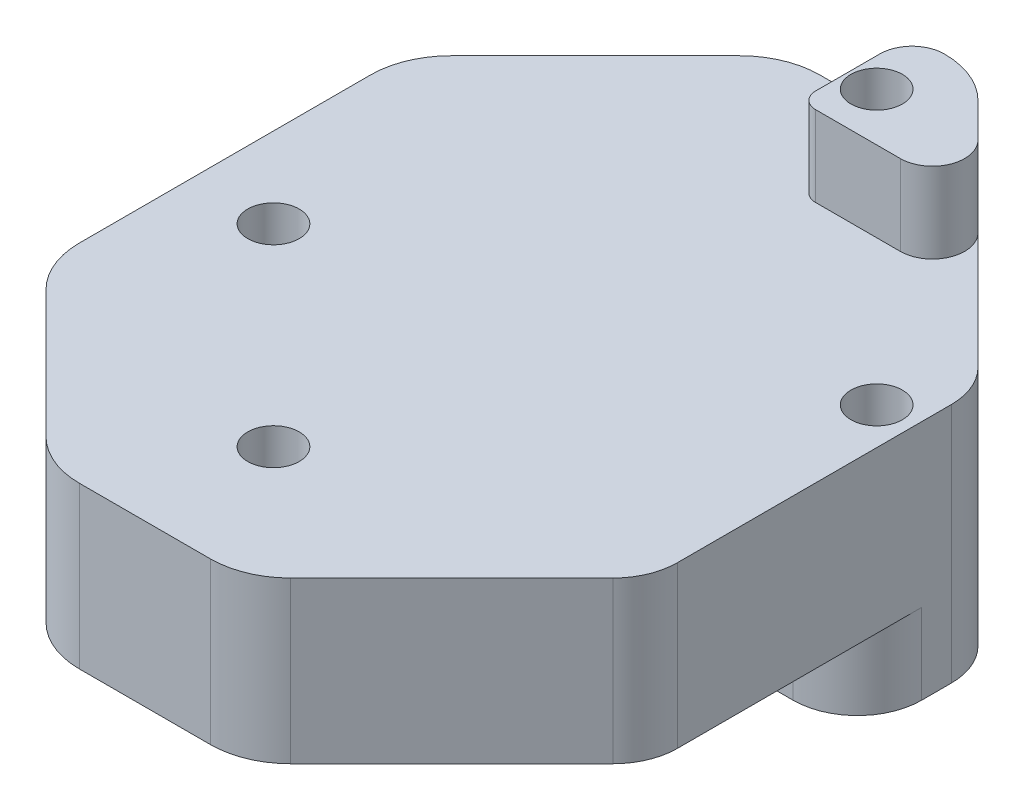
SolidWorks part; units mm, degrees
material "尼龙 101"
ref_plane "前视基准面" through (0, 0, 0) normal (0, 0, 1) x (1, 0, 0)
ref_plane "上视基准面" through (0, 0, 0) normal (0, 1, 0) x (1, 0, 0)
ref_plane "右视基准面" through (0, 0, 0) normal (1, 0, 0) x (0, 0, -1)
sketch "草图1" plane through (0, 0, 0) normal (0, 1, 0) x (1, 0, 0)
  line L0 (6.8, 37) -> (21.8, 22)
  line L1 (21.8, 22) -> (21.8, -8)
  line L2 (21.8, -8) -> (-17, -8)
  line L3 (-17, -8) -> (-17, 37)
  line L4 (-17, 37) -> (6.8, 37)
  circle A0 centre (0, 0) radius 1.6
  circle A1 centre (-12, 12) radius 1.6
  circle A2 centre (4.5, 33) radius 1.6
  circle A3 centre (16.5, 21) radius 1.6
  dimension "D1" = 12
  dimension "D2" = 3.2
  dimension "D3" = 12
  dimension "D4" = 16.5
  dimension "D5" = 21
  dimension "D6" = 12
  dimension "D7" = 12
  dimension "D10" = 5.3
  dimension "D9" = 5
  dimension "D8" = 135
  dimension "D11" = 8
  dimension "D12" = 30
  dimension "D13" = 45
extrude "凸台-拉伸1" add sketch "草图1" along normal blind 10
sketch "草图2" plane through (0, 0, 0) normal (0, -1, 0) x (1, 0, 0)
  line L0 (21.8, -17.5) -> (2, -17.5)
  line L1 (21.8, 8) -> (21.8, -22) construction
  line L2 (0, -19.5) -> (0, -37)
  line L3 (6.8, -37) -> (-17, -37) construction
  line L4 (0, -37) -> (6.8, -37)
  line L5 (6.8, -37) -> (21.8, -22)
  line L6 (21.8, -22) -> (21.8, -17.5)
  circle A0 centre (4.5, -33) radius 1.6 construction
  arc A2 (2, -17.5) -> (0, -19.5) centre (2, -19.5) ccw
  circle A3 centre (4.5, -33) radius 1.6
  circle A4 centre (16.5, -21) radius 1.6
  dimension "D1" = 15.5
  dimension "D2" = 2
  dimension "D3" = 3.2
  dimension "D4" = 3.2
extrude "凸台-拉伸2" add sketch "草图2" along normal blind 5
sketch "草图3" plane through (0, 10, 0) normal (0, 1, 0) x (1, 0, 0)
  line L0 (-5.1, 37) -> (-17, 25.1)
  line L1 (6.8, 37) -> (-17, 37) construction
  line L2 (-17, 37) -> (-17, -8) construction
  line L3 (-17, 25.1) -> (-17, 2.8579)
  line L4 (-17, 2.8579) -> (-6.1421, -8)
  line L5 (-17, -8) -> (21.8, -8) construction
  line L6 (-6.1421, -8) -> (6.1421, -8)
  line L7 (6.1421, -8) -> (21.8, 7.6579)
  line L8 (21.8, -8) -> (21.8, 22) construction
  line L9 (21.8, 7.6579) -> (21.8, 22)
  line L10 (21.8, 22) -> (6.8, 37) construction
  line L11 (21.8, 22) -> (6.8, 37)
  line L12 (6.8, 37) -> (-5.1, 37)
  circle A0 centre (0, 0) radius 1.6 construction
  dimension "D3" = 10
  dimension "D1" = 135
  dimension "D2" = 135
  dimension "D4" = 10
extrude "切除-拉伸1" cut sketch "草图3" against normal through all flip side to cut
fillet "圆角1" radius 5 8 edges at (21.8, 5, -7.6579) (6.1421, 5, 8) (-6.1421, 5, 8) (-17, 5, -2.8579) (-17, 5, -25.1) (-5.1, 5, -37) (21.8, 2.5, -22) (6.8, 2.5, -37)
fillet "圆角2" radius 2 2 edges at (0, -2.5, -37) (21.8, -2.5, -17.5)
sketch "草图4" plane through (0, 10, 0) normal (0, 1, 0) x (1, 0, 0)
  line L0 (2.7, 37) -> (2.7, 31)
  line L1 (4.7289, 37) -> (-3.0289, 37) construction
  line L2 (3.7, 30) -> (13.8, 30)
  line L3 (20.3355, 23.4645) -> (8.2645, 35.5355) construction
  line L4 (13.8, 30) -> (8.2645, 35.5355)
  line L5 (4.7289, 37) -> (2.7, 37)
  arc A0 (8.2645, 35.5355) -> (4.7289, 37) centre (4.7289, 32) ccw
  circle A1 centre (4.5, 33) radius 1.6 construction
  arc A2 (2.7, 31) -> (3.7, 30) centre (3.7, 31) ccw
  circle A3 centre (4.5, 33) radius 1.6
  dimension "D1" = 1.8
  dimension "D3" = 1
  dimension "D4" = 3.2
  dimension "D2" = 3
extrude "凸台-拉伸3" add sketch "草图4" along normal blind 5
fillet "圆角3" radius 2 2 edges at (2.7, 12.5, -37) (13.8, 12.5, -30)
sketch "草图5" plane through (0, 10, 0) normal (0, 1, 0) x (1, 0, 0)
  line L0 (18.8, 25) -> (18.8, 4.6579)
  line L1 (20.3355, 23.4645) -> (10.3858, 33.4142) construction
  line L2 (7.6066, -6.5355) -> (20.3355, 6.1934) construction
  line L13 (8.9716, 30) -> (3.7, 30)
  line L14 (2.7, 31) -> (2.7, 35)
  line L15 (4.7, 37) -> (-3.0289, 37)
  line L16 (-6.5645, 35.5355) -> (-15.5355, 26.5645)
  line L17 (-17, 23.0289) -> (-17, 4.9289)
  line L18 (-15.5355, 1.3934) -> (-7.6066, -6.5355)
  line L19 (-4.0711, -8) -> (4.0711, -8)
  line L20 (7.6066, -6.5355) -> (20.3355, 6.1934)
  line L21 (21.8, 9.7289) -> (21.8, 19.9289)
  line L22 (20.3355, 23.4645) -> (10.3858, 33.4142)
  line L30 (18.8, 4.6579) -> (20.3355, 6.1934)
  line L31 (21.8, 9.7289) -> (21.8, 19.9289)
  line L32 (20.3355, 23.4645) -> (18.8, 25)
  arc A8 (2.7, 31) -> (3.7, 30) centre (3.7, 31) ccw
  arc A9 (4.7, 37) -> (2.7, 35) centre (4.7, 35) ccw
  arc A12 (-3.0289, 37) -> (-6.5645, 35.5355) centre (-3.0289, 32) ccw
  arc A13 (-15.5355, 26.5645) -> (-17, 23.0289) centre (-12, 23.0289) ccw
  arc A14 (-17, 4.9289) -> (-15.5355, 1.3934) centre (-12, 4.9289) ccw
  arc A15 (-7.6066, -6.5355) -> (-4.0711, -8) centre (-4.0711, -3) ccw
  arc A16 (4.0711, -8) -> (7.6066, -6.5355) centre (4.0711, -3) ccw
  arc A17 (20.3355, 6.1934) -> (21.8, 9.7289) centre (16.8, 9.7289) ccw
  arc A18 (21.8, 19.9289) -> (20.3355, 23.4645) centre (16.8, 19.9289) ccw
  arc A19 (8.9716, 30) -> (10.3858, 33.4142) centre (8.9716, 32) ccw
  arc A27 (20.3355, 6.1934) -> (21.8, 9.7289) centre (16.8, 9.7289) ccw
  arc A28 (21.8, 19.9289) -> (20.3355, 23.4645) centre (16.8, 19.9289) ccw
  dimension "D2" = 3
  dimension "D1" = 0
extrude "切除-拉伸2" cut sketch "草图5" against normal blind 24
fillet "圆角4" radius 4 3 edges at (18.8, -2.5, -17.5) (18.8, 5, -4.6579) (18.8, 2.5, -25)
